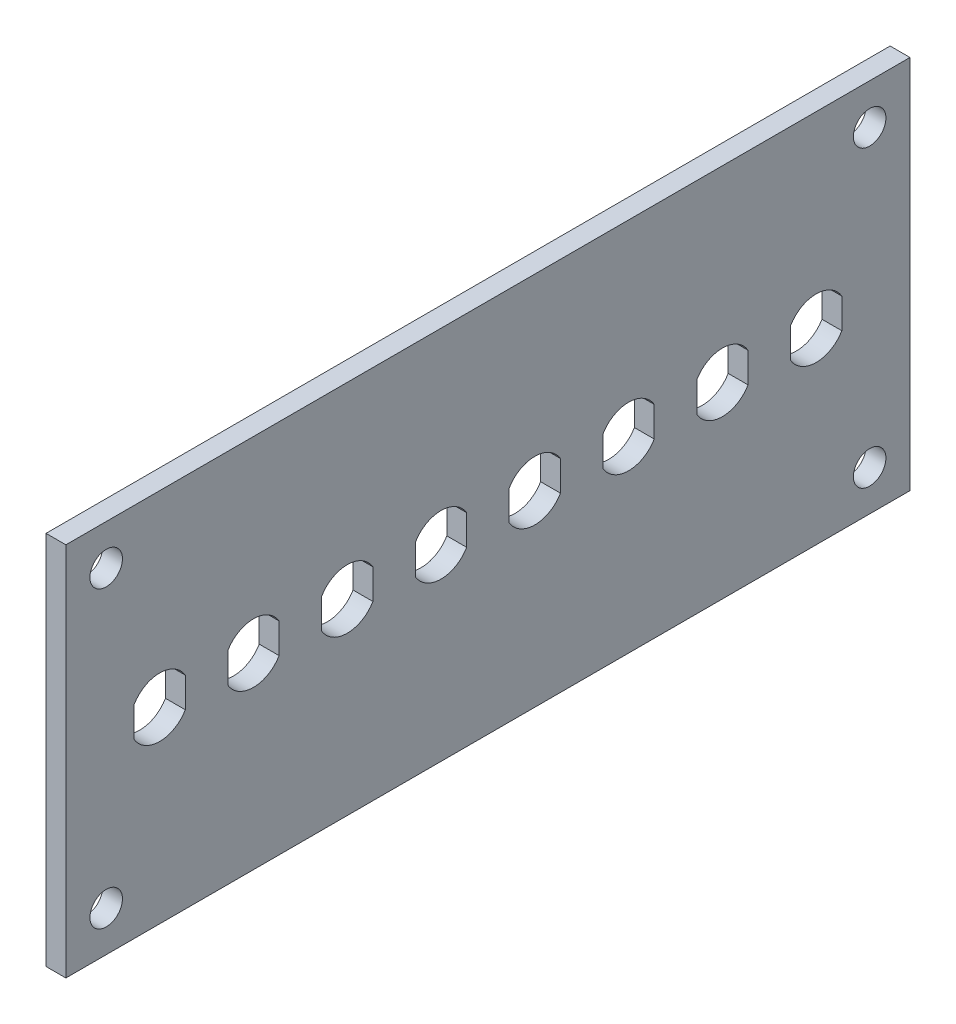
SolidWorks part; units mm, degrees
ref_plane "Front Plane" through (0, 0, 0) normal (0, 0, 1) x (1, 0, 0)
ref_plane "Top Plane" through (0, 0, 0) normal (0, 1, 0) x (1, 0, 0)
ref_plane "Right Plane" through (0, 0, 0) normal (1, 0, 0) x (0, 0, -1)
sketch "Sketch1" plane through (0, 0, 0) normal (1, 0, 0) x (0, 0, -1)
  line L1 (-67.5, -30) -> (67.5, -30)
  line L2 (-67.5, -30) -> (-67.5, 30)
  line L3 (-67.5, 30) -> (67.5, 30)
  line L4 (67.5, -30) -> (67.5, 30)
  line L5 (-67.5, -30) -> (67.5, 30) construction
  line L6 (-67.5, 30) -> (67.5, -30) construction
  point P0 (0, 0)
  dimension "D1" = 135
  dimension "D2" = 60
extrude "Boss-Extrude1" add sketch "Sketch1" along normal blind 1.5875 and the other way blind 1.5875
sketch "Sketch2" plane through (0, 0, 0) normal (1, 0, 0) x (0, 0, -1)
  line L0 (-67.5, 30) -> (-61.05, 30) construction
  line L1 (67.5, 30) -> (-67.5, 30) construction
  line L2 (-61.05, 30) -> (-61.05, 23.55) construction
  line L3 (0, 1.7463) -> (0, -1.7463) construction
  line L4 (1.7463, 0) -> (-1.7463, 0) construction
  circle A0 centre (-61.05, 23.55) radius 2.6
  circle A1 centre (61.05, 23.55) radius 2.6
  circle A2 centre (61.05, -23.55) radius 2.6
  circle A3 centre (-61.05, -23.55) radius 2.6
  dimension "D3" = 5.2
  dimension "D1" = 6.45
  dimension "D2" = 6.45
extrude "Cut-Extrude1" cut sketch "Sketch2" against normal through all both and the other way through all
sketch "Sketch3" plane through (0, 0, 0) normal (1, 0, 0) x (0, 0, -1)
  line L5 (-52.5, 0) -> (52.5, 0) construction
  line L18 (-56.6, 0) -> (-48.4, 0) construction
  line L19 (-56.6, -2.3984) -> (-56.6, 2.3984)
  line L21 (-48.4, -2.3984) -> (-48.4, 2.3984)
  arc A1 (-56.6, -2.3984) -> (-48.4, -2.3984) centre (-52.5, 0) ccw
  arc A2 (-48.4, 2.3984) -> (-56.6, 2.3984) centre (-52.5, 0) ccw
  point P3 (0, 0)
  point P7 (-52.5, 0)
  point P10 (-56.6, 0)
  point P13 (-48.4, 0)
  dimension "D3" = 9.5
  dimension "D1" = 105
  dimension "D2" = 8.2
extrude "Cut-Extrude2" cut sketch "Sketch3" against normal through all both and the other way through all
pattern_linear "LPattern1" count 8 spacing 15 along (0, 0, -1) of "Cut-Extrude2"
equation "\"Coax pitch\"= 15"
equation "\"D1@Sketch3\"=\"Coax pitch\"*7"
equation "\"D3@LPattern1\"=\"Coax pitch\""
